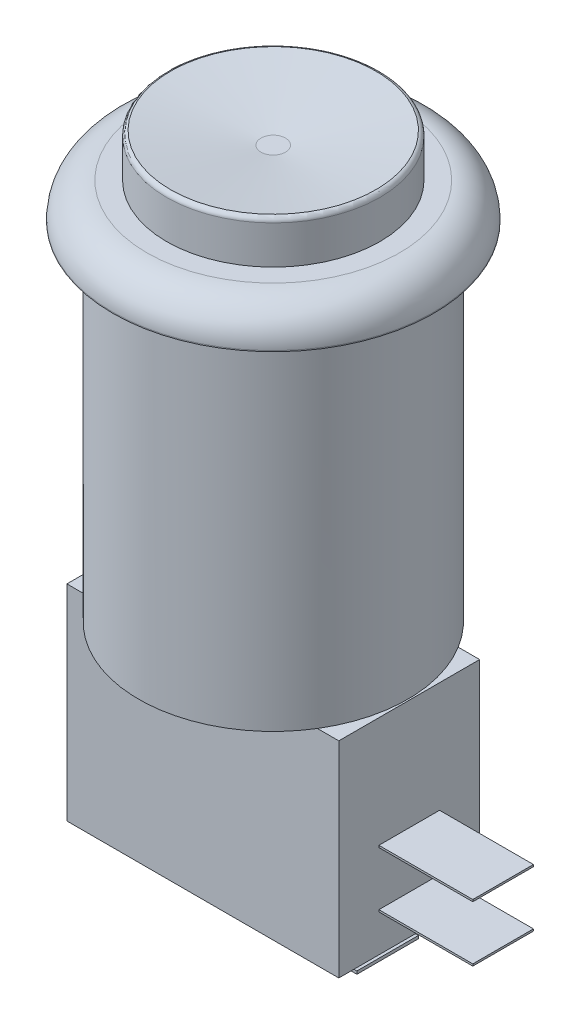
SolidWorks part; units mm, degrees
ref_plane "Front Plane" through (0, 0, 0) normal (0, 0, 1) x (1, 0, 0)
ref_plane "Top Plane" through (0, 0, 0) normal (0, 1, 0) x (1, 0, 0)
ref_plane "Right Plane" through (0, 0, 0) normal (1, 0, 0) x (0, 0, -1)
sketch "Sketch1" plane through (0, 0, 0) normal (0, 1, 0) x (1, 0, 0)
  circle A0 centre (0, 0) radius 13.75
  dimension "D1" = 27.5
extrude "Boss-Extrude1" add sketch "Sketch1" along normal blind 35.5
sketch "Sketch2" plane through (0, 35.5, 0) normal (0, 1, 0) x (1, 0, 0)
  circle A0 centre (0, 0) radius 16.4
  dimension "D1" = 32.8
extrude "Boss-Extrude2" add sketch "Sketch2" along normal blind 3.6
sketch "Sketch3" plane through (0, 39.1, 0) normal (0, 1, 0) x (1, 0, 0)
  circle A0 centre (0, 0) radius 10.9
  dimension "D1" = 21.8
extrude "Boss-Extrude3" add sketch "Sketch3" along normal blind 4.4
fillet "Fillet1" radius 3.5 1 edges at (0, 39.1, 16.4)
sketch "Sketch4" plane through (0, 43.5, 0) normal (0, 1, 0) x (1, 0, 0)
  circle A0 centre (0, 0) radius 0.5
extrude "Cut-Extrude1" cut sketch "Sketch4" against normal blind 1.3
chamfer "Chamfer1" distance 10 angle 8 1 edges at (0, 43.5, 0.5) first distance on face at (0, 43.5, 0.5)
fillet "Fillet2" radius 0.5 1 edges at (0, 43.5, 10.9)
sketch "Sketch5" plane through (0, 0, 0) normal (0, -1, 0) x (1, 0, 0)
  line L1 (-13.9, -7.2) -> (13.9, -7.2)
  line L2 (-13.9, -7.2) -> (-13.9, 7.2)
  line L3 (-13.9, 7.2) -> (13.9, 7.2)
  line L4 (13.9, -7.2) -> (13.9, 7.2)
  line L5 (-13.9, -7.2) -> (13.9, 7.2) construction
  line L6 (-13.9, 7.2) -> (13.9, -7.2) construction
  point P0 (0, 0)
  dimension "D1" = 14.4
  dimension "D2" = 27.8
extrude "Boss-Extrude4" add sketch "Sketch5" along normal blind 21
sketch "Sketch6" plane through (0, -21, 0) normal (0, -1, 0) x (1, 0, 0)
  line L0 (13.9, -7.2) -> (13.9, 7.2) construction
  line L1 (11.7, 3.15) -> (1.7, 3.15)
  line L2 (11.7, 3.15) -> (11.7, -3.15)
  line L3 (11.7, -3.15) -> (1.7, -3.15)
  line L4 (1.7, 3.15) -> (1.7, -3.15)
  line L5 (13.9, 7.2) -> (-13.9, 7.2) construction
  line L6 (-13.9, -7.2) -> (13.9, -7.2) construction
  dimension "D1" = 10
  dimension "D2" = 6.3
  dimension "D3" = 2.2
  dimension "D4" = 4.05
  dimension "D5" = 4.05
extrude "Boss-Extrude5" add sketch "Sketch6" along normal blind 2.8
sketch "Sketch7" plane through (11.7, 0, 0) normal (1, 0, 0) x (0, 0, -1)
  line L0 (-3.15, -23.8) -> (-3.15, -21) construction
  line L1 (3.15, -21) -> (-3.15, -21)
  line L2 (3.15, -21) -> (3.15, -23.5)
  line L3 (3.15, -23.5) -> (-3.15, -23.5)
  line L4 (-3.15, -21) -> (-3.15, -23.5)
  dimension "D1" = 2.5
extrude "Cut-Extrude2" cut sketch "Sketch7" against normal blind 9.8
sketch "Sketch8" plane through (13.9, 0, 0) normal (1, 0, 0) x (0, 0, -1)
  line L0 (7.2, -21) -> (7.2, 0) construction
  line L1 (3.1, -17.2) -> (-3.1, -17.2)
  line L2 (3.1, -17.2) -> (3.1, -17)
  line L3 (3.1, -17) -> (-3.1, -17)
  line L4 (-3.1, -17.2) -> (-3.1, -17)
  line L5 (-7.2, -21) -> (-7.2, 0) construction
  line L6 (7.2, -21) -> (-7.2, -21) construction
  line L8 (3.1, -11.5) -> (-3.1, -11.5)
  line L9 (3.1, -11.5) -> (3.1, -11.3)
  line L10 (3.1, -11.3) -> (-3.1, -11.3)
  line L11 (-3.1, -11.5) -> (-3.1, -11.3)
  dimension "D1" = 6.2
  dimension "D2" = 4.1
  dimension "D3" = 4.1
  dimension "D4" = 3.8
  dimension "D5" = 0.2
  dimension "D6" = 0.2
  dimension "D7" = 6.2
  dimension "D8" = 4.1
  dimension "D9" = 9.5
extrude "Boss-Extrude6" add sketch "Sketch8" along normal blind 9.6
